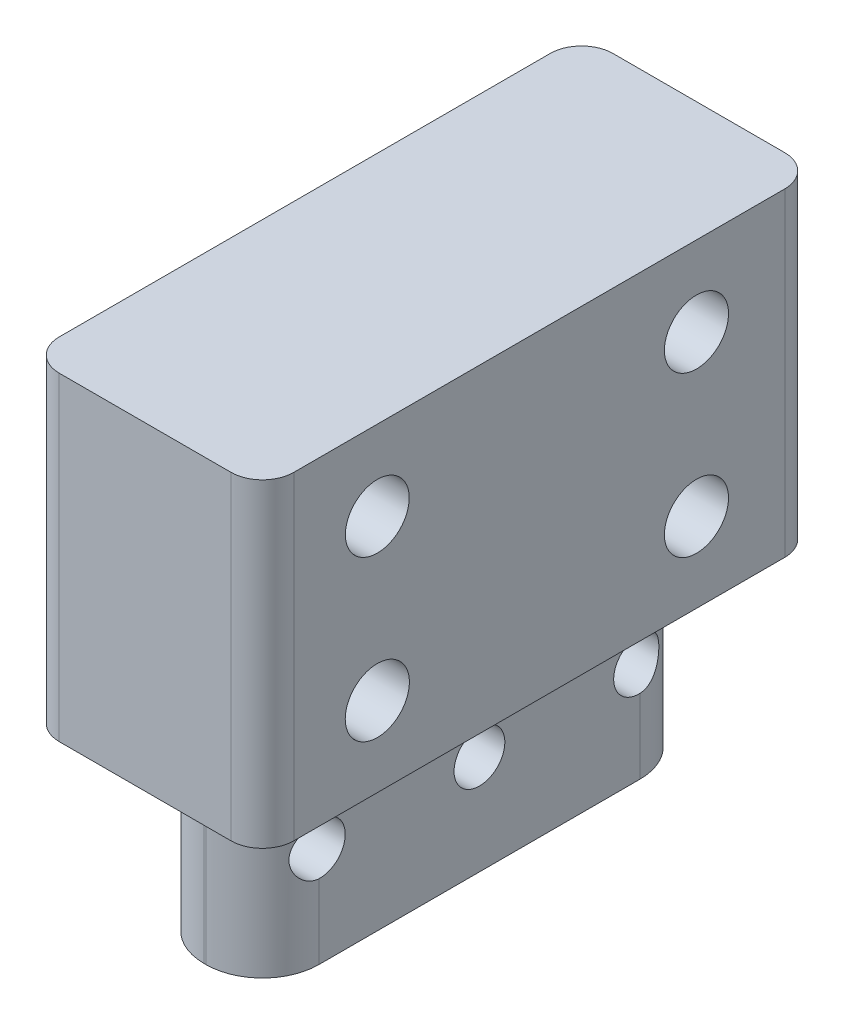
SolidWorks part; units mm, degrees
material "6061-T6 (SS)"
ref_plane "Front Plane" through (0, 0, 0) normal (0, 0, 1) x (1, 0, 0)
ref_plane "Top Plane" through (0, 0, 0) normal (0, 1, 0) x (1, 0, 0)
ref_plane "Right Plane" through (0, 0, 0) normal (1, 0, 0) x (0, 0, -1)
sketch "Sketch1" plane through (0, 0, 0) normal (0, 0, 1) x (1, 0, 0)
  line L1 (0, 0) -> (18.669, 0)
  line L2 (0, 0) -> (0, 50.8)
  line L3 (0, 50.8) -> (18.669, 50.8)
  line L4 (18.669, 0) -> (18.669, 50.8)
  dimension "D1" = 50.8
  dimension "D2" = 18.669
extrude "Boss-Extrude1" add sketch "Sketch1" along normal blind 44.069
sketch "Sketch2" plane through (18.669, 0, 0) normal (1, 0, 0) x (0, 0, -1)
  line L0 (-44.069, 0) -> (-44.069, 50.8) construction
  line L1 (0, 0) -> (-44.069, 0)
  line L2 (0, 0) -> (0, 4.7625)
  line L3 (0, 4.7625) -> (-44.069, 4.7625)
  line L4 (-44.069, 0) -> (-44.069, 4.7625)
  dimension "D1" = 4.7625
extrude "Cut-Extrude1" cut sketch "Sketch2" against normal through all
sketch "Sketch3" plane through (18.669, 0, 0) normal (1, 0, 0) x (0, 0, -1)
  line L0 (-44.069, 4.7625) -> (-44.069, 50.8) construction
  line L1 (0, 4.7625) -> (-44.069, 4.7625)
  line L2 (0, 4.7625) -> (0, 19.0525)
  line L3 (0, 19.0525) -> (-44.069, 19.0525)
  line L4 (-44.069, 4.7625) -> (-44.069, 19.0525)
  dimension "D1" = 14.29
sketch "Sketch4" plane through (0, 0, 44.069) normal (0, 0, 1) x (1, 0, 0)
  line L0 (18.669, 4.7625) -> (18.669, 19.0525) construction
  line L1 (18.669, 19.0525) -> (0, 19.0525)
  line L2 (18.669, 19.0525) -> (18.669, 4.7625)
  line L3 (18.669, 4.7625) -> (0, 4.7625)
  line L4 (0, 19.0525) -> (0, 4.7625)
  line L5 (18.669, 4.7625) -> (18.669, 50.8) construction
  dimension "D1" = 14.29
sketch "Sketch5" plane through (0, 0, 0) normal (-1, 0, 0) x (0, 0, 1)
  line L1 (44.069, 19.0525) -> (0, 19.0525)
  line L2 (44.069, 19.0525) -> (44.069, 4.7625)
  line L3 (44.069, 4.7625) -> (0, 4.7625)
  line L4 (0, 19.0525) -> (0, 4.7625)
sketch "Sketch6" plane through (0, 0, 0) normal (0, 0, -1) x (-1, 0, 0)
  line L1 (0, 19.0525) -> (-18.669, 19.0525)
  line L2 (0, 19.0525) -> (0, 4.7625)
  line L3 (0, 4.7625) -> (-18.669, 4.7625)
  line L4 (-18.669, 19.0525) -> (-18.669, 4.7625)
extrude "Cut-Extrude2" cut sketch "Sketch3" against normal blind 4.7625
extrude "Cut-Extrude3" cut sketch "Sketch5" against normal blind 4.7625
extrude "Cut-Extrude4" cut sketch "Sketch4" against normal blind 4.7625
extrude "Cut-Extrude5" cut sketch "Sketch6" against normal blind 4.7625
fillet "Fillet1" radius 4.5009 4 edges at (4.7625, 11.9075, 39.3065) (13.9065, 11.9075, 39.3065) (4.7625, 11.9075, 4.7625) (13.9065, 11.9075, 4.7625)
fillet "Fillet2" radius 2.4994 4 edges at (0, 34.9263, 44.069) (18.669, 34.9263, 44.069) (18.669, 34.9263, 0) (0, 34.9263, 0)
sketch "Sketch7" plane through (0, 0, 0) normal (-1, 0, 0) x (0, 0, 1)
  line L0 (41.5696, 50.8) -> (2.4994, 50.8) construction
  line L1 (2.4994, 50.8) -> (2.4994, 19.0525) construction
  line L2 (41.5696, 19.0525) -> (41.5696, 50.8) construction
  line L3 (41.5696, 19.0525) -> (2.4994, 19.0525) construction
  circle A0 centre (9.5259, 38.1) radius 2.5527
  circle A1 centre (34.9259, 38.1) radius 2.54
  circle A2 centre (34.9259, 25.4) radius 2.5527
  circle A3 centre (9.5259, 25.4) radius 2.5527
  dimension "D1" = 25.4
  dimension "D2" = 12.7
  dimension "D3" = 5.1054
  dimension "D4" = 7.0265
  dimension "D5" = 6.6438
  dimension "D6" = 5.08
  dimension "D7" = 5.1054
  dimension "D8" = 7.0265
  dimension "D9" = 6.3475
  dimension "D10" = 25.4
  dimension "D11" = 5.1054
  dimension "D12" = 6.6438
extrude "Cut-Extrude6" cut sketch "Sketch7" against normal through all
sketch "Sketch8" plane through (4.7625, 0, 0) normal (-1, 0, 0) x (0, 0, 1)
  line L0 (9.2634, 4.7625) -> (34.8056, 4.7625) construction
  line L2 (9.2634, 19.0525) -> (9.2634, 4.7625) construction
  circle A0 centre (22.0354, 12.7) radius 2.0193
  circle A1 centre (34.7354, 12.7) radius 2.0193
  circle A2 centre (9.3354, 12.7) radius 2.0193
  dimension "D1" = 4.0386
  dimension "D2" = 4.0386
  dimension "D3" = 4.0386
  dimension "D4" = 7.9375
  dimension "D5" = 12.7
  dimension "D6" = 7.9375
  dimension "D7" = 12.772
  dimension "D8" = 12.7
  dimension "D9" = 7.9375
extrude "Cut-Extrude7" cut sketch "Sketch8" against normal through all
sketch "Sketch10" plane through (0, 0, 0) normal (0, 0, -1) x (-1, 0, 0)
  line L0 (-16.1696, 50.8) -> (-2.4994, 50.8) construction
  line L1 (-18.669, 50.8) -> (0, 50.8)
  line L2 (-18.669, 50.8) -> (-18.669, 44.45)
  line L3 (-18.669, 44.45) -> (0, 44.45)
  line L4 (0, 50.8) -> (0, 44.45)
  line L6 (-18.669, 19.0525) -> (-18.669, 50.8) construction
  line L7 (0, 50.8) -> (0, 19.0525) construction
  point P4 (0, 0)
  dimension "D1" = 6.35
extrude "Cut-Extrude8" cut sketch "Sketch10" against normal through all
